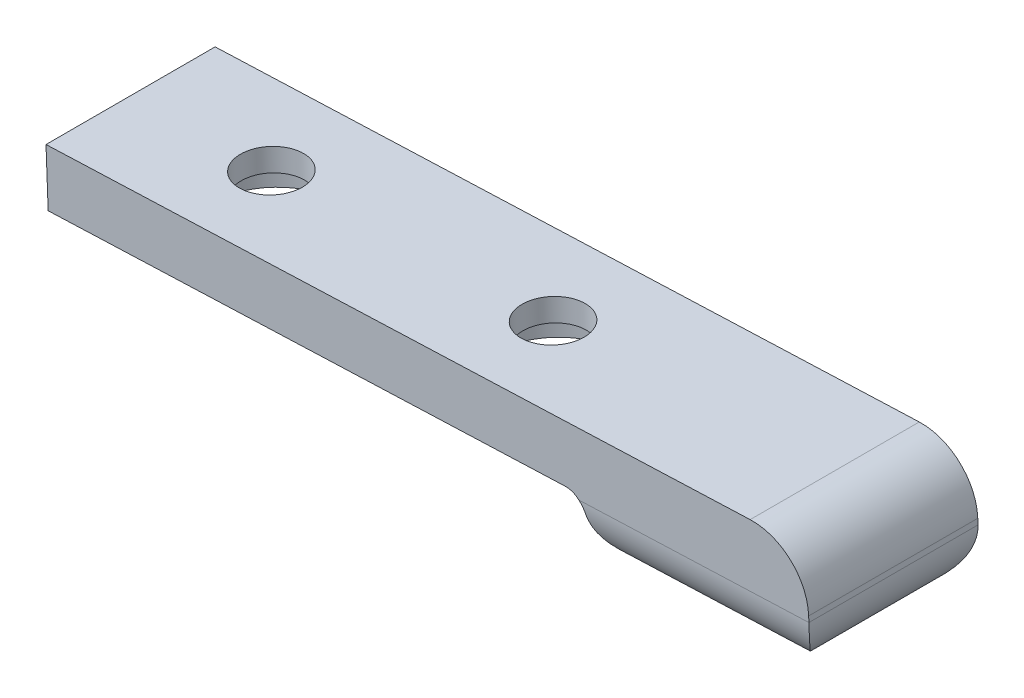
SolidWorks part; units mm, degrees
ref_plane "Front Plane" through (0, 0, 0) normal (0, 0, 1) x (1, 0, 0)
ref_plane "Top Plane" through (0, 0, 0) normal (0, 1, 0) x (1, 0, 0)
ref_plane "Right Plane" through (0, 0, 0) normal (1, 0, 0) x (0, 0, -1)
sketch "Sketch1" plane through (-0.4272, 11.0539, 0) normal (0.0386, -0.9993, 0) x (0.9993, 0.0386, 0)
  line L10 (-27.2546, 108) -> (-18.4546, 108) construction
  line L11 (-27.2546, 108) -> (-18.4546, 108)
  line L12 (-18.4546, 102) -> (-27.2546, 102) construction
  line L13 (-18.4546, 102) -> (-27.2546, 102)
  line L14 (-27.2546, 108) -> (-34.2546, 108)
  line L15 (-34.2546, 108) -> (-34.2546, 102)
  line L16 (-34.2546, 102) -> (-27.2546, 102)
  line L17 (-18.4546, 102) -> (-7.2546, 102)
  line L18 (-7.2546, 102) -> (-7.2546, 108)
  line L19 (-7.2546, 108) -> (-18.4546, 108)
  circle A0 centre (-19.2546, 105) radius 1.1 construction
  circle A1 centre (-29.2546, 105) radius 1.1 construction
  circle A2 centre (-19.2546, 105) radius 1.1
  circle A3 centre (-29.2546, 105) radius 1.1
  dimension "D1" = 5
  dimension "D2" = 12
extrude "Boss-Extrude1" add sketch "Sketch1" along normal blind 2
sketch "Sketch2" plane through (-0.35, 9.0554, 0) normal (0.0386, -0.9993, 0) x (0.9993, 0.0386, 0)
  line L0 (-34.2546, 102) -> (-7.2546, 102) construction
  line L1 (-7.2546, 108) -> (-15.2546, 108)
  line L2 (-7.2546, 108) -> (-7.2546, 102)
  line L3 (-7.2546, 102) -> (-15.2546, 102)
  line L4 (-15.2546, 108) -> (-15.2546, 102)
  dimension "D1" = 8
extrude "Boss-Extrude2" add sketch "Sketch2" along normal blind 2.2
fillet "Fillet1" radius 2 4 edges at (-11.5112, 6.4224, 102) (-15.5082, 6.2679, 105) (-11.5112, 6.4224, 108) (-7.5142, 6.5769, 105)
fillet "Fillet6" radius 2 1 edges at (-7.6764, 10.7737, 105)
sketch "Sketch3" plane through (-0.35, 9.0554, 0) normal (0.0386, -0.9993, 0) x (0.9993, 0.0386, 0)
  circle A0 centre (-19.2546, 105) radius 2.25
  circle A2 centre (-29.2546, 105) radius 1.1 construction
  circle A3 centre (-29.2546, 105) radius 1.1
  circle A4 centre (-29.2546, 105) radius 2.25
  dimension "D1" = 4.5
extrude "Cut-Extrude1" cut sketch "Sketch3" against normal blind 1.2
fillet "Fillet7" radius 0.7 1 edges at (-15.5932, 8.4663, 105)
